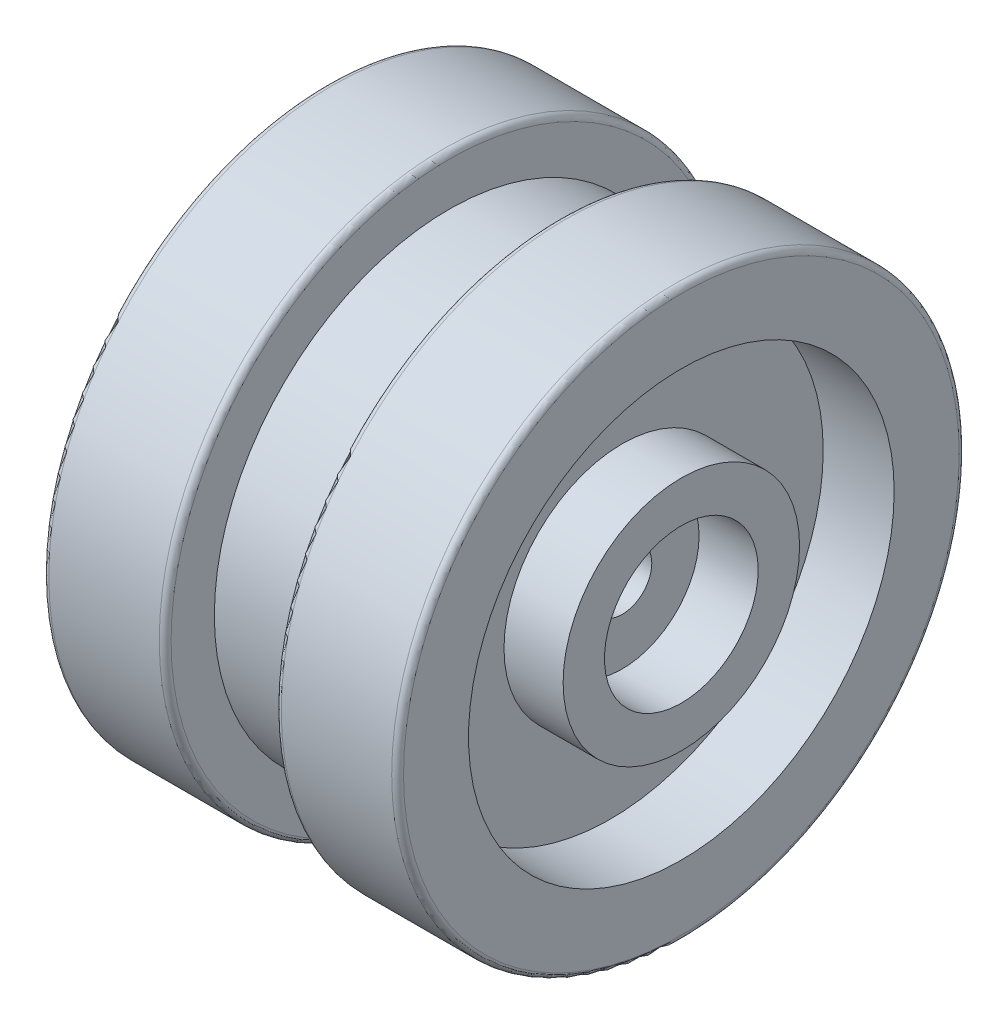
SolidWorks part; units mm, degrees
ref_plane "Front Plane" through (0, 0, 0) normal (0, 0, 1) x (1, 0, 0)
ref_plane "Top Plane" through (0, 0, 0) normal (0, 1, 0) x (1, 0, 0)
ref_plane "Right Plane" through (0, 0, 0) normal (1, 0, 0) x (0, 0, -1)
sketch "Sketch2" plane through (0, 0, 0) normal (0, 0, 1) x (1, 0, 0)
  line L0 (-2.0852, 1.3557) -> (7.2348, 1.3557)
  line L1 (-2.0852, 1.3557) -> (-2.0852, 5.5157)
  line L2 (7.2348, 1.3557) -> (7.2348, 5.5157)
  line L3 (7.2348, 5.5157) -> (17.5748, 5.5157)
  line L4 (-2.0852, 5.5157) -> (-12.4252, 5.5157)
  line L5 (-12.4252, 5.5157) -> (-12.4252, -18.4843)
  line L6 (-12.4252, -18.4843) -> (17.5748, -18.4843)
  line L7 (17.5748, -18.4843) -> (17.5748, 5.5157)
  line L8 (-12.4252, -18.4843) -> (27.3603, -18.4843) construction
  dimension "D1" = 30
  dimension "D2" = 24
  dimension "D4" = 4.16
  dimension "D5" = 9.32
revolve "Revolve1" add sketch "Sketch2" angle 360 about L8
sketch "Sketch3" plane through (17.5748, 0, 0) normal (1, 0, 0) x (0, 0, -1)
  circle A0 centre (0, -18.4843) radius 2
extrude "Cut-Extrude1" cut sketch "Sketch3" against normal through all
fillet "Fillet2" radius 0.5 4 edges at (-2.0852, -18.4843, 24) (7.2348, -18.4843, 24) (17.5748, -18.4843, 24) (-12.4252, -18.4843, 24)
sketch "Sketch4" plane through (17.5748, 0, 0) normal (1, 0, 0) x (0, 0, -1)
  circle A0 centre (0, -18.4843) radius 6
  circle A1 centre (0, -18.4843) radius 18
extrude "Cut-Extrude2" cut sketch "Sketch4" against normal blind 6
sketch "Sketch5" plane through (-12.4252, 0, 0) normal (-1, 0, 0) x (0, 0, 1)
  circle A0 centre (0, -18.4843) radius 6
  circle A1 centre (0, -18.4843) radius 18
extrude "Cut-Extrude3" cut sketch "Sketch5" against normal blind 6 contours A1
sketch "Sketch6" plane through (-6.4252, 0, 0) normal (-1, 0, 0) x (0, 0, 1)
  circle A0 centre (0, -18.4843) radius 10
extrude "Boss-Extrude1" add sketch "Sketch6" along normal through all
sketch "Sketch7" plane through (-12.4252, 0, 0) normal (-1, 0, 0) x (0, 0, 1)
  circle A0 centre (0, -18.4843) radius 2.5
sketch "Sketch8" plane through (17.5748, 0, 0) normal (1, 0, 0) x (0, 0, -1)
  circle A0 centre (0, -18.4843) radius 8
extrude "Boss-Extrude2" add sketch "Sketch8" against normal blind 10 contours A0
sketch "Sketch9" plane through (17.5748, 0, 0) normal (1, 0, 0) x (0, 0, -1)
  circle A0 centre (0, -18.4843) radius 6.5
sketch "Sketch10" plane through (-12.4252, 0, 0) normal (-1, 0, 0) x (0, 0, 1)
  circle A0 centre (0, -18.4843) radius 6.5
extrude "Cut-Extrude5" cut sketch "Sketch10" against normal blind 5 contours A0
sketch "Sketch11" plane through (17.5748, 0, 0) normal (1, 0, 0) x (0, 0, -1)
  circle A0 centre (0, -18.4843) radius 10
extrude "Boss-Extrude3" add sketch "Sketch11" against normal blind 5
sketch "Sketch12" plane through (17.5748, 0, 0) normal (1, 0, 0) x (0, 0, -1)
  circle A0 centre (0, -18.4843) radius 6.5
extrude "Cut-Extrude6" cut sketch "Sketch12" against normal blind 5
extrude "Cut-Extrude8" cut sketch "Sketch7" against normal through all contours A0
